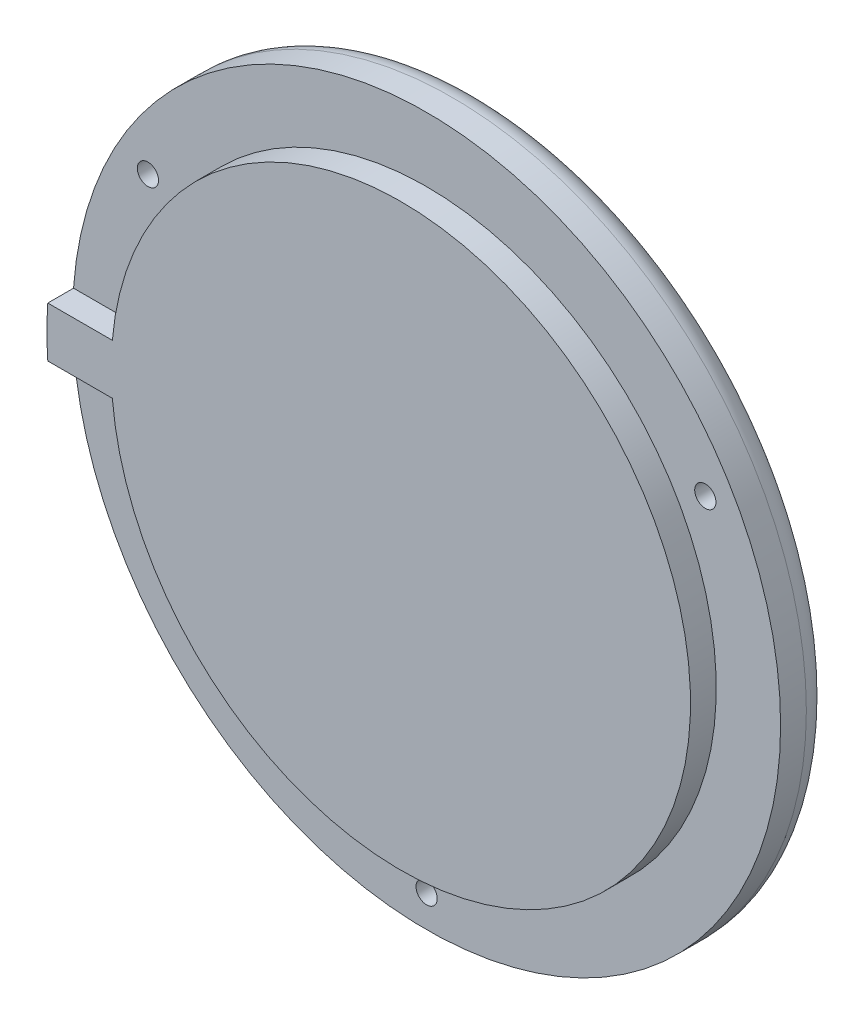
SolidWorks part; units mm, degrees
ref_plane "Plano frontal" through (0, 0, 0) normal (0, 0, 1) x (1, 0, 0)
ref_plane "Plano superior" through (0, 0, 0) normal (0, 1, 0) x (1, 0, 0)
ref_plane "Plano direito" through (0, 0, 0) normal (1, 0, 0) x (0, 0, -1)
sketch "Esboço1" plane through (0, 0, 0) normal (0, 0, 1) x (1, 0, 0)
  circle A0 centre (0, 0) radius 55
  dimension "D1" = 110
extrude "Ressalto-extrusão1" add sketch "Esboço1" along normal blind 8
sketch "Esboço2" plane through (0, 0, 8) normal (0, 0, 1) x (1, 0, 0)
  line L3 (-44.8307, 3.9) -> (-54.8616, 3.9)
  line L5 (-44.8307, -3.9) -> (-54.8616, -3.9)
  arc A0 (-44.8307, -3.9) -> (-44.8307, 3.9) centre (0, 0) ccw
  arc A1 (-54.8616, 3.9) -> (-54.8616, -3.9) centre (0, 0) ccw
  dimension "D1" = 110
  dimension "D2" = 90
  dimension "D3" = 10.0309
  dimension "D4" = 10.0309
extrude "Ressalto-extrusão2" add sketch "Esboço2" along normal blind 4
sketch "Esboço3" plane through (0, 0, 8) normal (0, 0, 1) x (1, 0, 0)
  circle A0 centre (0, -50) radius 1.65
  arc A2 (-54.8616, -3.9) -> (-54.8616, 3.9) centre (0, 0) ccw construction
  circle A3 centre (-43.3012, 25) radius 1.65
  circle A4 centre (43.3013, 25) radius 1.65
  point P9 (55, 0)
  point P14 (0, 0)
  dimension "D1" = 3.3
  dimension "D4" = 3
  dimension "D5" = 75
  dimension "D6" = 86.6025
  dimension "D2" = 50
  dimension "D3" = 55
extrude "Corte-extrusão1" cut sketch "Esboço3" against normal blind 3
sketch "Esboço4" plane through (0, 0, 5) normal (0, 0, 1) x (1, 0, 0)
  circle A0 centre (-43.3012, 25) radius 2.9
  circle A1 centre (43.3013, 25) radius 2.9
  circle A2 centre (0, -50) radius 2.9
  dimension "D1" = 5.8
  dimension "D2" = 5.8
  dimension "D3" = 5.8
extrude "Corte-extrusão2" cut sketch "Esboço4" against normal up to surface (5 mm away) up to face at (55, 0, 0)
fillet "Filete1" radius 4 1 edges at (55, 0, 0)
